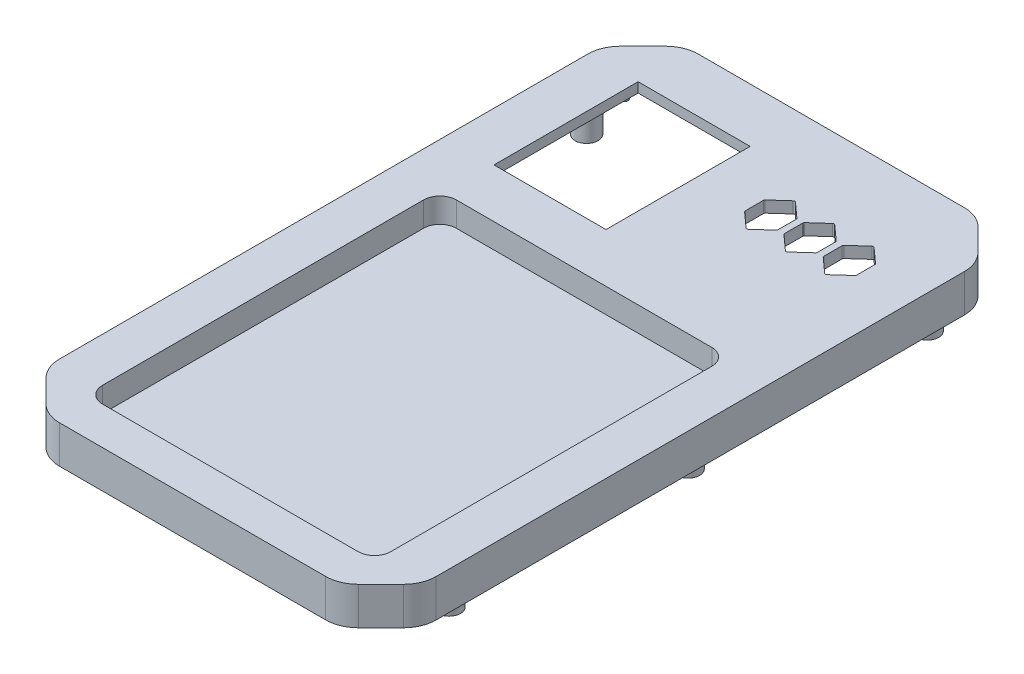
SolidWorks part; units mm, degrees
ref_plane "Front Plane" through (0, 0, 0) normal (0, 0, 1) x (1, 0, 0)
ref_plane "Top Plane" through (0, 0, 0) normal (0, 1, 0) x (1, 0, 0)
ref_plane "Right Plane" through (0, 0, 0) normal (1, 0, 0) x (0, 0, -1)
sketch "Sketch1" plane through (0, 0, 0) normal (0, 1, 0) x (1, 0, 0)
  line L0 (12.7279, 12.7279) -> (102.2721, 12.7279)
  line L1 (115, 0) -> (115, -169.5442)
  line L2 (102.2721, -182.2721) -> (12.7279, -182.2721)
  line L3 (0, -169.5442) -> (0, 0)
  line L4 (12.7279, 12.7279) -> (0, 0)
  line L5 (102.2721, 12.7279) -> (115, 0)
  line L6 (0, -169.5442) -> (12.7279, -182.2721)
  line L7 (115, -169.5442) -> (102.2721, -182.2721)
  dimension "D1" = 115
  dimension "D2" = 195
  dimension "D3" = 135
  dimension "D4" = 135
  dimension "D5" = 135
  dimension "D6" = 135
  dimension "D7" = 18
extrude "Boss-Extrude4" add sketch "Sketch1" along normal blind 20
fillet "Fillet4" radius 10 8 edges at (115, 10, 0) (115, 10, 169.5442) (12.7279, 10, 182.2721) (0, 10, 169.5442) (0, 10, 0) (12.7279, 10, -12.7279) (102.2721, 10, -12.7279) (102.2721, 10, 182.2721)
sketch "Sketch5" plane through (0, 20, 0) normal (0, 1, 0) x (1, 0, 0)
  line L0 (0, -4.1421) -> (0, -165.402) construction
  line L2 (16.8701, -182.2721) -> (98.1299, -182.2721) construction
  line L4 (15, -3.7721) -> (49.2, -3.7721)
  line L5 (15, -3.7721) -> (15, -47.7721)
  line L6 (15, -47.7721) -> (49.2, -47.7721)
  line L7 (49.2, -3.7721) -> (49.2, -47.7721)
  line L8 (96.5, -62.7721) -> (18.5, -62.7721)
  line L9 (101.5, -165.7721) -> (101.5, -67.7721)
  line L10 (18.5, -170.7721) -> (96.5, -170.7721)
  line L11 (13.5, -67.7721) -> (13.5, -165.7721)
  arc A1 (18.5, -62.7721) -> (13.5, -67.7721) centre (18.5, -67.7721) ccw
  arc A2 (96.5, -170.7721) -> (101.5, -165.7721) centre (96.5, -165.7721) ccw
  arc A3 (101.5, -67.7721) -> (96.5, -62.7721) centre (96.5, -67.7721) ccw
  arc A4 (13.5, -165.7721) -> (18.5, -170.7721) centre (18.5, -165.7721) ccw
  dimension "D3" = 13.5
  dimension "D9" = 10
  dimension "D1" = 34.2
  dimension "D5" = 88
  dimension "D2" = 44
  dimension "D4" = 11.5
  dimension "D6" = 108
  dimension "D7" = 15
  dimension "D8" = 15
extrude "Cut-Extrude4" cut sketch "Sketch5" against normal blind 7.5
ref_plane "Plane1" through (0, 6.25, 0) normal (0, 1, 0) x (1, 0, 0)
sketch "Sketch23" plane through (0, 20, 0) normal (0, 1, 0) x (1, 0, 0)
  line L0 (99.5, -21.7721) -> (99.5, -15.7721)
  line L23 (99.5, -15.7721) -> (94.5, -11.2721)
  line L24 (94.5, -11.2721) -> (89.5, -15.7721)
  line L29 (89.5, -15.7721) -> (89.5, -21.7721)
  line L30 (89.5, -21.7721) -> (94.5, -26.2721)
  line L35 (94.5, -26.2721) -> (99.5, -21.7721)
  line L36 (87.5, -21.7721) -> (87.5, -15.7721)
  line L37 (75.5, -21.7721) -> (75.5, -15.7721)
  line L38 (75.5, -15.7721) -> (70.5, -11.2721)
  line L39 (70.5, -11.2721) -> (65.5, -15.7721)
  line L40 (65.5, -15.7721) -> (65.5, -21.7721)
  line L41 (65.5, -21.7721) -> (70.5, -26.2721)
  line L42 (70.5, -26.2721) -> (75.5, -21.7721)
  line L43 (87.5, -15.7721) -> (82.5, -11.2721)
  line L44 (82.5, -11.2721) -> (77.5, -15.7721)
  line L45 (77.5, -15.7721) -> (77.5, -21.7721)
  line L46 (77.5, -21.7721) -> (82.5, -26.2721)
  line L47 (82.5, -26.2721) -> (87.5, -21.7721)
  line L50 (94.5, -11.2721) -> (94.5, -26.2721) construction
  line L51 (89.5, -18.7721) -> (99.5, -18.7721) construction
  line L52 (98.1299, 12.7279) -> (16.8701, 12.7279) construction
  line L53 (82.5, -11.2721) -> (82.5, -26.2721) construction
  line L54 (70.5, -11.2721) -> (70.5, -26.2721) construction
  line L55 (115, -165.402) -> (115, -4.1421) construction
  point P16 (94.5, -18.7721)
  dimension "D1" = 10
  dimension "D2" = 15
  dimension "D3" = 10
  dimension "D4" = 15
  dimension "D5" = 10
  dimension "D6" = 15
  dimension "D7" = 20.5
  dimension "D8" = 12
  dimension "D9" = 6
  dimension "D10" = 12
  dimension "D11" = 31.5
sketch "Sketch28" plane through (0, 0, 0) normal (0, -1, 0) x (1, 0, 0)
  line L0 (98.1299, -12.7279) -> (16.8701, -12.7279) construction
  line L1 (105, 57.2721) -> (56, 57.2721)
  line L2 (105, 57.2721) -> (105, 22.2721)
  line L3 (105, 22.2721) -> (56, 22.2721)
  line L4 (56, 57.2721) -> (56, 22.2721)
  line L5 (115, 165.402) -> (115, 4.1421) construction
  dimension "D5" = 10
  dimension "D6" = 49
  dimension "D7" = 35
  dimension "D1" = 35
extrude "Cut-Extrude17" cut sketch "Sketch28" against normal blind 13
shell "Shell2" thickness 1.5
extrude "Cut-Extrude15" cut sketch "Sketch23" against normal up to next
fillet "Fillet3" radius 0.5 18 edges at (82.5, 19.25, 26.2721) (94.5, 19.25, 26.2721) (89.5, 19.25, 21.7721) (89.5, 19.25, 15.7721) (77.5, 19.25, 21.7721) (77.5, 19.25, 15.7721) (70.5, 19.25, 26.2721) (65.5, 19.25, 21.7721) (75.5, 19.25, 21.7721) (75.5, 19.25, 15.7721) (87.5, 19.25, 15.7721) (99.5, 19.25, 21.7721) (99.5, 19.25, 15.7721) (94.5, 19.25, 11.2721) (82.5, 19.25, 11.2721) (65.5, 19.25, 15.7721) (70.5, 19.25, 11.2721) (87.5, 19.25, 21.7721)
sketch "Sketch29" plane through (0, 12.5, 0) normal (0, 1, 0) x (1, 0, 0)
  line L4 (49.2, -3.7721) -> (15, -3.7721)
  line L5 (15, -3.7721) -> (15, -47.7721)
  line L6 (15, -47.7721) -> (49.2, -47.7721)
  line L7 (49.2, -47.7721) -> (49.2, -3.7721)
  line L8 (49.2, -3.7721) -> (15, -3.7721)
  line L9 (15, -3.7721) -> (15, -47.7721)
  line L10 (15, -47.7721) -> (49.2, -47.7721)
  line L11 (49.2, -47.7721) -> (49.2, -3.7721)
  dimension "D1" = 0
extrude "Cut-Extrude18" cut sketch "Sketch29" against normal up to next
sketch "Sketch30" plane through (0, 13, 0) normal (0, -1, 0) x (1, 0, 0)
  line L0 (58, 45.1221) -> (103, 45.1221)
  line L3 (58, 46.5721) -> (103, 46.5721)
  line L6 (58, 34.4221) -> (103, 34.4221)
  line L8 (56, 57.2721) -> (56, 22.2721) construction
  line L9 (105, 22.2721) -> (105, 57.2721) construction
  line L10 (58, 32.9721) -> (103, 32.9721)
  line L14 (105, 22.2721) -> (105, 57.2721) construction
  line L15 (105, 57.2721) -> (56, 57.2721) construction
  line L20 (103, 49.3221) -> (104, 49.3221)
  line L21 (56, 22.2721) -> (105, 22.2721) construction
  line L22 (57, 49.3221) -> (58, 49.3221)
  line L23 (57, 49.3221) -> (57, 42.8221)
  line L24 (57, 42.8221) -> (58, 42.8221)
  line L25 (58, 49.3221) -> (58, 46.5721)
  line L26 (103, 49.3221) -> (103, 46.5721)
  line L27 (103, 42.8221) -> (104, 42.8221)
  line L28 (57, 37.1721) -> (58, 37.1721)
  line L29 (57, 37.1721) -> (57, 30.6721)
  line L30 (57, 30.6721) -> (58, 30.6721)
  line L31 (58, 37.1721) -> (58, 34.4221)
  line L32 (104, 49.3221) -> (104, 42.8221)
  line L33 (103, 37.1721) -> (104, 37.1721)
  line L34 (103, 37.1721) -> (103, 34.4221)
  line L35 (103, 30.6721) -> (104, 30.6721)
  line L36 (104, 37.1721) -> (104, 30.6721)
  line L37 (58, 45.1221) -> (58, 42.8221)
  line L38 (103, 45.1221) -> (103, 42.8221)
  line L39 (103, 32.9721) -> (103, 30.6721)
  line L40 (58, 32.9721) -> (58, 30.6721)
  point P14 (57.5, 42.8221)
  point P33 (57.5, 30.6721)
  dimension "D1" = 10.7
  dimension "D2" = 10.7
  dimension "D3" = 1.45
  dimension "D4" = 10.7
  dimension "D5" = 1
  dimension "D6" = 6.5
  dimension "D7" = 2.75
  dimension "D8" = 1
  dimension "D9" = 2.75
  dimension "D10" = 1
  dimension "D11" = 6.5
  dimension "D12" = 1
  dimension "D13" = 1
  dimension "D14" = 1
extrude "Boss-Extrude11" add sketch "Sketch30" along normal blind 9 contours L40 L10 L39 L35 L36 L33 L34 L6 L31 L28 L29 L30 | L0 L38 L27 L32 L20 L26 L3 L25 L22 L23 L24 L37 | L0 L38 L27 L32 L20 L26 L3 L25 L22 L23 L24 L37 | L28 L31 L6 L34 L33 L36 L35 L39 L10 L40 L30 L29 region at (80.5, 13, 45.8845) region at (80.5, 13, 33.7345)
sketch "Sketch33" plane through (0, 14.5, 0) normal (0, 1, 0) x (1, 0, 0)
  line L6 (54.5, -50.1721) -> (56, -50.1721)
  line L7 (54.5, -50.1721) -> (54.5, -54.7721)
  line L8 (54.5, -54.7721) -> (56, -54.7721)
  line L9 (56, -50.1721) -> (56, -54.7721)
  line L10 (106.5, -58.7721) -> (54.5, -58.7721) construction
  line L11 (105, -24.7721) -> (106.5, -24.7721)
  line L12 (105, -24.7721) -> (105, -29.3721)
  line L13 (105, -29.3721) -> (106.5, -29.3721)
  line L14 (106.5, -24.7721) -> (106.5, -29.3721)
  line L15 (106.5, -20.7721) -> (106.5, -58.7721) construction
  line L16 (54.5, -20.7721) -> (106.5, -20.7721) construction
  line L18 (54.5, -58.7721) -> (54.5, -20.7721) construction
  line L22 (56, -57.2721) -> (105, -57.2721)
  line L23 (56, -22.2721) -> (56, -57.2721)
  line L24 (105, -22.2721) -> (56, -22.2721)
  line L25 (105, -57.2721) -> (105, -22.2721)
  line L26 (56, -57.2721) -> (105, -57.2721)
  line L27 (56, -22.2721) -> (56, -57.2721)
  line L28 (105, -22.2721) -> (56, -22.2721)
  line L29 (105, -57.2721) -> (105, -22.2721)
  dimension "D1" = 4
  dimension "D2" = 4.6
  dimension "D4" = 4.6
  dimension "D6" = 4
  dimension "D7" = 0
extrude "Cut-Extrude19" cut sketch "Sketch33" against normal blind 3 contours L7 L8 L9 L6 | L14 L13 L12 L11
sketch "Sketch34" plane through (0, 0, 0) normal (0, -1, 0) x (1, 0, 0)
  line L0 (105, 57.2721) -> (56, 57.2721) construction
  line L1 (106, 58.2721) -> (55, 58.2721)
  line L2 (106, 58.2721) -> (106, 21.2721)
  line L3 (106, 21.2721) -> (55, 21.2721)
  line L4 (55, 58.2721) -> (55, 21.2721)
  line L5 (56, 22.2721) -> (105, 22.2721) construction
  line L6 (56, 57.2721) -> (56, 22.2721) construction
  line L7 (104, 37.1721) -> (104, 30.6721) construction
  dimension "D1" = 1
  dimension "D2" = 1
  dimension "D3" = 1
  dimension "D4" = 2
extrude "Cut-Extrude22" cut sketch "Sketch34" against normal blind 3
sketch "Sketch37" plane through (0, 1.5, 0) normal (0, 1, 0) x (1, 0, 0)
  line L0 (54.5, -20.7721) -> (106.5, -20.7721) construction
  line L1 (68, -9.7721) -> (93, -9.7721)
  line L2 (68, -9.7721) -> (68, -20.7721)
  line L3 (68, -20.7721) -> (93, -20.7721)
  line L4 (93, -9.7721) -> (93, -20.7721)
  line L6 (54.5, -20.7721) -> (106.5, -20.7721) construction
  point P8 (80.5, -20.7721)
  dimension "D1" = 11
  dimension "D2" = 25
extrude "Boss-Extrude13" add sketch "Sketch37" along normal blind 7
sketch "Sketch35" plane through (0, 0, 0) normal (0, -1, 0) x (1, 0, 0)
  line L0 (55, 21.2721) -> (106, 21.2721) construction
  line L1 (55, 21.2721) -> (106, 21.2721) construction
  line L2 (88.5, 21.2721) -> (72.5, 21.2721)
  arc A0 (88.5, 21.2721) -> (72.5, 21.2721) centre (80.5, 21.2721) cw
  point P7 (80.5, 13.2721)
  dimension "D1" = 8
extrude "Cut-Extrude25" cut sketch "Sketch35" against normal blind 3
sketch "Sketch38" plane through (0, 3, 0) normal (0, -1, 0) x (1, 0, 0)
  line L0 (56, 22.2721) -> (105, 22.2721) construction
  circle A0 centre (80.5, 18.2721) radius 1.5
  dimension "D1" = 3
  dimension "D2" = 4
  dimension "D3" = 8
extrude "Cut-Extrude26" cut sketch "Sketch38" against normal blind 5
sketch "Sketch39" plane through (0, 0, 58.2721) normal (0, 0, -1) x (-1, 0, 0)
  line L0 (-106, 3) -> (-55, 3) construction
  line L1 (-98, 3) -> (-91, 3)
  line L2 (-98, 3) -> (-98, 1)
  line L3 (-98, 1) -> (-91, 1)
  line L4 (-91, 3) -> (-91, 1)
  line L5 (-105, 3) -> (-56, 3) construction
  line L6 (-103, 4) -> (-103, 13) construction
  line L7 (-70, 3) -> (-63, 3)
  line L8 (-70, 3) -> (-70, 1)
  line L9 (-70, 1) -> (-63, 1)
  line L10 (-63, 3) -> (-63, 1)
  line L12 (-58, 4) -> (-58, 13) construction
  dimension "D1" = 7
  dimension "D2" = 2
  dimension "D3" = 5
  dimension "D4" = 7
  dimension "D5" = 2
  dimension "D6" = 5
extrude "Cut-Extrude27" cut sketch "Sketch39" against normal blind 5
ref_plane "Plane5" through (0, 8.8, 0) normal (0, -1, 0) x (-1, 0, 0)
sketch "Sketch40" plane through (0, 0, 0) normal (0, -1, 0) x (1, 0, 0)
  line L8 (105.201, -9.799) -> (112.0711, -2.9289)
  line L9 (115, 4.1421) -> (115, 165.402)
  line L10 (112.0711, 172.4731) -> (105.201, 179.3431)
  line L11 (98.1299, 182.2721) -> (16.8701, 182.2721)
  line L12 (9.799, 179.3431) -> (2.9289, 172.4731)
  line L13 (0, 165.402) -> (0, 4.1421)
  line L14 (2.9289, -2.9289) -> (9.799, -9.799)
  line L15 (16.8701, -12.7279) -> (98.1299, -12.7279)
  line L16 (105.201, -9.799) -> (112.0711, -2.9289)
  line L17 (115, 4.1421) -> (115, 165.402)
  line L18 (112.0711, 172.4731) -> (105.201, 179.3431)
  line L19 (98.1299, 182.2721) -> (16.8701, 182.2721)
  line L20 (9.799, 179.3431) -> (2.9289, 172.4731)
  line L21 (0, 165.402) -> (0, 4.1421)
  line L22 (2.9289, -2.9289) -> (9.799, -9.799)
  line L23 (16.8701, -12.7279) -> (98.1299, -12.7279)
  line L24 (98.1299, 177.2721) -> (16.8701, 177.2721)
  line L25 (13.3345, 175.8076) -> (6.4645, 168.9376)
  line L26 (5, 165.402) -> (5, 4.1421)
  line L27 (6.4645, 0.6066) -> (13.3345, -6.2635)
  line L28 (16.8701, -7.7279) -> (98.1299, -7.7279)
  line L29 (101.6655, -6.2635) -> (108.5355, 0.6066)
  line L30 (110, 4.1421) -> (110, 165.402)
  line L31 (108.5355, 168.9376) -> (101.6655, 175.8076)
  arc A0 (16.8701, 177.2721) -> (13.3345, 175.8076) centre (16.8701, 172.2721) ccw
  arc A1 (6.4645, 168.9376) -> (5, 165.402) centre (10, 165.402) ccw
  arc A2 (5, 4.1421) -> (6.4645, 0.6066) centre (10, 4.1421) ccw
  arc A3 (13.3345, -6.2635) -> (16.8701, -7.7279) centre (16.8701, -2.7279) ccw
  arc A4 (98.1299, -7.7279) -> (101.6655, -6.2635) centre (98.1299, -2.7279) ccw
  arc A5 (108.5355, 0.6066) -> (110, 4.1421) centre (105, 4.1421) ccw
  arc A6 (110, 165.402) -> (108.5355, 168.9376) centre (105, 165.402) ccw
  arc A7 (101.6655, 175.8076) -> (98.1299, 177.2721) centre (98.1299, 172.2721) ccw
  arc A8 (112.0711, -2.9289) -> (115, 4.1421) centre (105, 4.1421) ccw
  arc A9 (112.0711, -2.9289) -> (115, 4.1421) centre (105, 4.1421) ccw
  arc A10 (115, 165.402) -> (112.0711, 172.4731) centre (105, 165.402) ccw
  arc A11 (115, 165.402) -> (112.0711, 172.4731) centre (105, 165.402) ccw
  arc A12 (105.201, 179.3431) -> (98.1299, 182.2721) centre (98.1299, 172.2721) ccw
  arc A13 (105.201, 179.3431) -> (98.1299, 182.2721) centre (98.1299, 172.2721) ccw
  arc A14 (16.8701, 182.2721) -> (9.799, 179.3431) centre (16.8701, 172.2721) ccw
  arc A15 (16.8701, 182.2721) -> (9.799, 179.3431) centre (16.8701, 172.2721) ccw
  arc A16 (2.9289, 172.4731) -> (0, 165.402) centre (10, 165.402) ccw
  arc A17 (2.9289, 172.4731) -> (0, 165.402) centre (10, 165.402) ccw
  arc A18 (0, 4.1421) -> (2.9289, -2.9289) centre (10, 4.1421) ccw
  arc A19 (0, 4.1421) -> (2.9289, -2.9289) centre (10, 4.1421) ccw
  arc A20 (9.799, -9.799) -> (16.8701, -12.7279) centre (16.8701, -2.7279) ccw
  arc A21 (9.799, -9.799) -> (16.8701, -12.7279) centre (16.8701, -2.7279) ccw
  arc A22 (98.1299, -12.7279) -> (105.201, -9.799) centre (98.1299, -2.7279) ccw
  arc A23 (98.1299, -12.7279) -> (105.201, -9.799) centre (98.1299, -2.7279) ccw
  dimension "D1" = 0
  dimension "D2" = 5
extrude "Cut-Extrude28" cut sketch "Sketch40" against normal blind 10
delete or keep bodies "Body-Delete/Keep 1" type delete bodies bodies 175
sketch "Sketch42" plane through (0, 10, 0) normal (0, -1, 0) x (1, 0, 0)
  line L8 (16.8701, -12.7279) -> (98.1299, -12.7279)
  line L9 (105.201, -9.799) -> (112.0711, -2.9289)
  line L10 (115, 4.1421) -> (115, 165.402)
  line L11 (112.0711, 172.4731) -> (105.201, 179.3431)
  line L12 (98.1299, 182.2721) -> (16.8701, 182.2721)
  line L13 (9.799, 179.3431) -> (2.9289, 172.4731)
  line L14 (0, 165.402) -> (0, 4.1421)
  line L15 (2.9289, -2.9289) -> (9.799, -9.799)
  line L16 (16.8701, -12.7279) -> (98.1299, -12.7279)
  line L17 (105.201, -9.799) -> (112.0711, -2.9289)
  line L18 (115, 4.1421) -> (115, 165.402)
  line L19 (112.0711, 172.4731) -> (105.201, 179.3431)
  line L20 (98.1299, 182.2721) -> (16.8701, 182.2721)
  line L21 (9.799, 179.3431) -> (2.9289, 172.4731)
  line L22 (0, 165.402) -> (0, 4.1421)
  line L23 (2.9289, -2.9289) -> (9.799, -9.799)
  line L24 (10.2233, 178.9189) -> (3.3532, 172.0488)
  line L25 (0.6, 165.402) -> (0.6, 4.1421)
  line L26 (3.3532, -2.5047) -> (10.2233, -9.3747)
  line L27 (16.8701, -12.1279) -> (98.1299, -12.1279)
  line L28 (104.7767, -9.3747) -> (111.6468, -2.5047)
  line L29 (114.4, 4.1421) -> (114.4, 165.402)
  line L30 (111.6468, 172.0488) -> (104.7767, 178.9189)
  line L31 (98.1299, 181.6721) -> (16.8701, 181.6721)
  arc A0 (16.8701, 181.6721) -> (10.2233, 178.9189) centre (16.8701, 172.2721) ccw
  arc A1 (3.3532, 172.0488) -> (0.6, 165.402) centre (10, 165.402) ccw
  arc A2 (0.6, 4.1421) -> (3.3532, -2.5047) centre (10, 4.1421) ccw
  arc A3 (10.2233, -9.3747) -> (16.8701, -12.1279) centre (16.8701, -2.7279) ccw
  arc A4 (98.1299, -12.1279) -> (104.7767, -9.3747) centre (98.1299, -2.7279) ccw
  arc A5 (111.6468, -2.5047) -> (114.4, 4.1421) centre (105, 4.1421) ccw
  arc A6 (114.4, 165.402) -> (111.6468, 172.0488) centre (105, 165.402) ccw
  arc A7 (104.7767, 178.9189) -> (98.1299, 181.6721) centre (98.1299, 172.2721) ccw
  arc A8 (112.0711, -2.9289) -> (115, 4.1421) centre (105, 4.1421) ccw
  arc A9 (112.0711, -2.9289) -> (115, 4.1421) centre (105, 4.1421) ccw
  arc A10 (115, 165.402) -> (112.0711, 172.4731) centre (105, 165.402) ccw
  arc A11 (115, 165.402) -> (112.0711, 172.4731) centre (105, 165.402) ccw
  arc A12 (105.201, 179.3431) -> (98.1299, 182.2721) centre (98.1299, 172.2721) ccw
  arc A13 (105.201, 179.3431) -> (98.1299, 182.2721) centre (98.1299, 172.2721) ccw
  arc A14 (16.8701, 182.2721) -> (9.799, 179.3431) centre (16.8701, 172.2721) ccw
  arc A15 (16.8701, 182.2721) -> (9.799, 179.3431) centre (16.8701, 172.2721) ccw
  arc A16 (2.9289, 172.4731) -> (0, 165.402) centre (10, 165.402) ccw
  arc A17 (2.9289, 172.4731) -> (0, 165.402) centre (10, 165.402) ccw
  arc A18 (0, 4.1421) -> (2.9289, -2.9289) centre (10, 4.1421) ccw
  arc A19 (0, 4.1421) -> (2.9289, -2.9289) centre (10, 4.1421) ccw
  arc A20 (9.799, -9.799) -> (16.8701, -12.7279) centre (16.8701, -2.7279) ccw
  arc A21 (9.799, -9.799) -> (16.8701, -12.7279) centre (16.8701, -2.7279) ccw
  arc A22 (98.1299, -12.7279) -> (105.201, -9.799) centre (98.1299, -2.7279) ccw
  arc A23 (98.1299, -12.7279) -> (105.201, -9.799) centre (98.1299, -2.7279) ccw
  dimension "D1" = 0
  dimension "D2" = 0.6
extrude "Boss-Extrude14" add sketch "Sketch42" along normal blind 1.5
sketch "Sketch45" plane through (0, 0, 0) normal (0, 1, 0) x (1, 0, 0)
  line L0 (5.5, -10) -> (5.5, -83) construction
  line L1 (5.5, -83) -> (5.5, -156) construction
  line L2 (5.5, -156) -> (109.5, -156) construction
  line L3 (109.5, -156) -> (109.5, -83) construction
  line L4 (109.5, -83) -> (109.5, -10) construction
  line L5 (109.5, -10) -> (5.5, -10) construction
  line L6 (5.5, -83) -> (109.5, -83) construction
  line L7 (57.5, 12.7279) -> (57.5, -30.3618) construction
  line L8 (98.1299, 12.7279) -> (16.8701, 12.7279) construction
  circle A0 centre (5.5, -10) radius 4
  circle A1 centre (109.5, -10) radius 4
  circle A2 centre (109.5, -156) radius 4
  circle A3 centre (5.5, -156) radius 4
  circle A4 centre (5.5, -83) radius 4
  circle A5 centre (109.5, -83) radius 4
  dimension "D5" = 8
  dimension "D1" = 10
  dimension "D2" = 73
  dimension "D3" = 104
sketch "Sketch46" plane through (0, 18.5, 0) normal (0, -1, 0) x (1, 0, 0)
  circle A0 centre (5.5, 83) radius 3.5
  circle A1 centre (5.5, 10) radius 3.5
  circle A2 centre (109.5, 10) radius 3.5
  circle A3 centre (109.5, 83) radius 3.5
  circle A4 centre (109.5, 156) radius 3.5
  circle A5 centre (5.5, 156) radius 3.5
  dimension "D2" = 7
extrude "Boss-Extrude16" add sketch "Sketch46" along normal blind 14
sketch "Sketch51" plane through (0, 4.5, 0) normal (0, -1, 0) x (1, 0, 0)
  circle A0 centre (5.5, 156) radius 0.6
  dimension "D1" = 1.2
sketch "Sketch52" plane through (0, 4.5, 0) normal (0, -1, 0) x (1, 0, 0)
  circle A1 centre (5.5, 10) radius 0.6
  circle A2 centre (109.5, 10) radius 0.6
  circle A6 centre (5.5, 156) radius 0.6 construction
  circle A7 centre (5.5, 156) radius 0.6
  circle A8 centre (109.5, 156) radius 0.6
  circle A9 centre (109.5, 83) radius 0.6
  circle A10 centre (5.5, 83) radius 0.6
extrude "Cut-Extrude30" cut sketch "Sketch52" against normal blind 12
ref_plane "Plane6" through (70, 0, 0) normal (1, 0, 0) x (0, 0, -1)
sketch "Sketch53" plane through (70, 0, 0) normal (1, 0, 0) x (0, 0, -1)
  line L0 (-61.2721, 11) -> (-61.2721, 12.079)
  line L1 (-61.2721, 11) -> (-61.2721, 18.5) construction
  line L2 (-61.2721, 12.079) -> (-62.5603, 11)
  line L3 (-67.7721, 11) -> (-61.2721, 11) construction
  line L4 (-62.5603, 11) -> (-61.2721, 11)
  dimension "D1" = 1.079
  dimension "D2" = 1.6804
extrude "Cut-Extrude31" cut sketch "Sketch53" against normal up to next and the other way up to next
sketch "Sketch54" plane through (0, 11, 0) normal (0, -1, 0) x (1, 0, 0)
  line L4 (50.7, 2.2721) -> (50.7, 49.2721)
  line L5 (50.7, 49.2721) -> (13.5, 49.2721)
  line L6 (13.5, 49.2721) -> (13.5, 2.2721)
  line L7 (13.5, 2.2721) -> (50.7, 2.2721)
  line L8 (50.7, 2.2721) -> (50.7, 49.2721)
  line L9 (50.7, 49.2721) -> (13.5, 49.2721)
  line L10 (13.5, 49.2721) -> (13.5, 2.2721)
  line L11 (13.5, 2.2721) -> (50.7, 2.2721)
  dimension "D1" = 0
extrude "Cut-Extrude33" cut sketch "Sketch54" against normal blind 6
sketch "Sketch57" plane through (0, 17, 0) normal (0, -1, 0) x (1, 0, 0)
  line L0 (32.1, 47.7721) -> (32.1, 3.7721) construction
  line L1 (9.6, -1.2279) -> (54.6, -1.2279)
  line L2 (9.6, -1.2279) -> (9.6, 52.7721)
  line L3 (9.6, 52.7721) -> (54.6, 52.7721)
  line L4 (54.6, -1.2279) -> (54.6, 52.7721)
  line L5 (9.6, -1.2279) -> (54.6, 52.7721) construction
  line L6 (9.6, 52.7721) -> (54.6, -1.2279) construction
  line L7 (15, 47.7721) -> (49.2, 47.7721) construction
  line L8 (49.2, 3.7721) -> (15, 3.7721) construction
  line L9 (15, 25.7721) -> (49.2, 25.7721) construction
  line L10 (15, 3.7721) -> (15, 47.7721) construction
  line L11 (49.2, 47.7721) -> (49.2, 3.7721) construction
  line L12 (50.7, 49.2721) -> (50.7, 2.2721) construction
  line L13 (50.7, 2.2721) -> (13.5, 2.2721) construction
  line L14 (13.5, 49.2721) -> (13.5, 2.2721) construction
  line L15 (50.7, 49.2721) -> (13.5, 49.2721) construction
  line L16 (50.7, 49.2721) -> (50.7, 2.2721)
  line L17 (50.7, 2.2721) -> (13.5, 2.2721)
  line L18 (13.5, 49.2721) -> (13.5, 2.2721)
  line L19 (50.7, 49.2721) -> (13.5, 49.2721)
  point P0 (32.1, 25.7721)
  dimension "D1" = 45
  dimension "D2" = 54
extrude "Boss-Extrude17" add sketch "Sketch57" against normal up to next
sketch "Sketch58" plane through (0, 17, 0) normal (0, -1, 0) x (1, 0, 0)
  line L0 (9.6, 52.7721) -> (9.6, -1.2279) construction
  line L1 (9.6, 52.7721) -> (54.6, 52.7721) construction
  circle A0 centre (12.3, 5.3321) radius 1.2
  circle A1 centre (52.4, 5.3321) radius 1.2
  circle A2 centre (52.4, 50.3321) radius 1.2
  circle A3 centre (12.3, 50.3321) radius 1.2
  dimension "D1" = 2.4
  dimension "D2" = 2.7
  dimension "D3" = 2.44
  dimension "D4" = 45
  dimension "D5" = 40.1
extrude "Boss-Extrude18" add sketch "Sketch58" along normal blind 2
sketch "Sketch59" plane through (0, 11, 0) normal (0, -1, 0) x (1, 0, 0)
  line L0 (12, 59.2721) -> (103, 59.2721)
  line L1 (96.5, 61.2721) -> (18.5, 61.2721) construction
  line L4 (14.6158, 62.5603) -> (100.3842, 62.5603)
  line L5 (103, 67.7721) -> (103, 165.7721)
  line L6 (96.5, 172.2721) -> (18.5, 172.2721)
  line L7 (12, 165.7721) -> (12, 67.7721)
  line L9 (103, 59.2721) -> (103, 165.7721)
  line L10 (96.5, 172.2721) -> (18.5, 172.2721)
  line L11 (12, 165.7721) -> (12, 59.2721)
  arc A4 (100.3842, 62.5603) -> (103, 67.7721) centre (96.5, 67.7721) ccw
  arc A5 (103, 165.7721) -> (96.5, 172.2721) centre (96.5, 165.7721) ccw
  arc A6 (18.5, 172.2721) -> (12, 165.7721) centre (18.5, 165.7721) ccw
  arc A7 (12, 67.7721) -> (14.6158, 62.5603) centre (18.5, 67.7721) ccw
  arc A9 (103, 165.7721) -> (96.5, 172.2721) centre (96.5, 165.7721) ccw
  arc A10 (18.5, 172.2721) -> (12, 165.7721) centre (18.5, 165.7721) ccw
  dimension "D2" = 2
  dimension "D1" = 0
extrude "Cut-Extrude34" cut sketch "Sketch59" against normal blind 0.5
sketch "Sketch60" plane through (0, 18.5, 0) normal (0, -1, 0) x (1, 0, 0)
  line L6 (94.1655, 25.971) -> (89.6655, 21.921)
  line L7 (99.3345, 21.921) -> (94.8345, 25.971)
  line L8 (99.5, 15.9948) -> (99.5, 21.5494)
  line L9 (94.8345, 11.5731) -> (99.3345, 15.6231)
  line L10 (89.6655, 15.6231) -> (94.1655, 11.5731)
  line L11 (89.5, 21.5494) -> (89.5, 15.9948)
  line L12 (94.1655, 25.971) -> (89.6655, 21.921)
  line L13 (99.3345, 21.921) -> (94.8345, 25.971)
  line L14 (99.5, 15.9948) -> (99.5, 21.5494)
  line L15 (94.8345, 11.5731) -> (99.3345, 15.6231)
  line L16 (89.6655, 15.6231) -> (94.1655, 11.5731)
  line L17 (89.5, 21.5494) -> (89.5, 15.9948)
  line L18 (82.1655, 25.971) -> (77.6655, 21.921)
  line L19 (87.3345, 21.921) -> (82.8345, 25.971)
  line L20 (87.5, 15.9948) -> (87.5, 21.5494)
  line L21 (82.8345, 11.5731) -> (87.3345, 15.6231)
  line L22 (77.6655, 15.6231) -> (82.1655, 11.5731)
  line L23 (77.5, 21.5494) -> (77.5, 15.9948)
  line L24 (82.1655, 25.971) -> (77.6655, 21.921)
  line L25 (87.3345, 21.921) -> (82.8345, 25.971)
  line L26 (87.5, 15.9948) -> (87.5, 21.5494)
  line L27 (82.8345, 11.5731) -> (87.3345, 15.6231)
  line L28 (77.6655, 15.6231) -> (82.1655, 11.5731)
  line L29 (77.5, 21.5494) -> (77.5, 15.9948)
  line L30 (70.1655, 25.971) -> (65.6655, 21.921)
  line L31 (75.3345, 21.921) -> (70.8345, 25.971)
  line L32 (75.5, 15.9948) -> (75.5, 21.5494)
  line L33 (70.8345, 11.5731) -> (75.3345, 15.6231)
  line L34 (65.6655, 15.6231) -> (70.1655, 11.5731)
  line L35 (65.5, 21.5494) -> (65.5, 15.9948)
  line L36 (70.1655, 25.971) -> (65.6655, 21.921)
  line L37 (75.3345, 21.921) -> (70.8345, 25.971)
  line L38 (75.5, 15.9948) -> (75.5, 21.5494)
  line L39 (70.8345, 11.5731) -> (75.3345, 15.6231)
  line L40 (65.6655, 15.6231) -> (70.1655, 11.5731)
  line L41 (65.5, 21.5494) -> (65.5, 15.9948)
  line L48 (69.3628, 26.863) -> (64.8628, 22.813)
  line L49 (64.3, 21.5494) -> (64.3, 15.9948)
  line L50 (64.8628, 14.7312) -> (69.3628, 10.6812)
  line L51 (71.6372, 10.6812) -> (76.1372, 14.7312)
  line L53 (76.1372, 22.813) -> (71.6372, 26.863)
  line L54 (81.3628, 26.863) -> (76.8628, 22.813)
  line L56 (76.8628, 14.7312) -> (81.3628, 10.6812)
  line L57 (83.6372, 10.6812) -> (88.1372, 14.7312)
  line L59 (88.1372, 22.813) -> (83.6372, 26.863)
  line L60 (93.3628, 26.863) -> (88.8628, 22.813)
  line L62 (88.8628, 14.7312) -> (93.3628, 10.6812)
  line L63 (95.6372, 10.6812) -> (100.1372, 14.7312)
  line L64 (100.7, 15.9948) -> (100.7, 21.5494)
  line L76 (100.1372, 22.813) -> (95.6372, 26.863)
  line L88 (76.7, 15.9948) -> (76.7, 21.5494) construction
  line L89 (76.3, 21.5494) -> (76.3, 15.9948) construction
  line L90 (88.7, 15.9948) -> (88.7, 21.5494) construction
  line L91 (88.3, 21.5494) -> (88.3, 15.9948) construction
  arc A5 (82.8345, 25.971) -> (82.1655, 25.971) centre (82.5, 25.5994) ccw
  arc A6 (94.8345, 25.971) -> (94.1655, 25.971) centre (94.5, 25.5994) ccw
  arc A7 (99.5, 21.5494) -> (99.3345, 21.921) centre (99, 21.5494) ccw
  arc A8 (99.3345, 15.6231) -> (99.5, 15.9948) centre (99, 15.9948) ccw
  arc A9 (94.1655, 11.5731) -> (94.8345, 11.5731) centre (94.5, 11.9448) ccw
  arc A10 (89.5, 15.9948) -> (89.6655, 15.6231) centre (90, 15.9948) ccw
  arc A11 (89.6655, 21.921) -> (89.5, 21.5494) centre (90, 21.5494) ccw
  arc A12 (94.8345, 25.971) -> (94.1655, 25.971) centre (94.5, 25.5994) ccw
  arc A13 (99.5, 21.5494) -> (99.3345, 21.921) centre (99, 21.5494) ccw
  arc A14 (99.3345, 15.6231) -> (99.5, 15.9948) centre (99, 15.9948) ccw
  arc A15 (94.1655, 11.5731) -> (94.8345, 11.5731) centre (94.5, 11.9448) ccw
  arc A16 (89.5, 15.9948) -> (89.6655, 15.6231) centre (90, 15.9948) ccw
  arc A17 (89.6655, 21.921) -> (89.5, 21.5494) centre (90, 21.5494) ccw
  arc A18 (87.3345, 15.6231) -> (87.5, 15.9948) centre (87, 15.9948) ccw
  arc A19 (82.1655, 11.5731) -> (82.8345, 11.5731) centre (82.5, 11.9448) ccw
  arc A20 (77.5, 15.9948) -> (77.6655, 15.6231) centre (78, 15.9948) ccw
  arc A21 (77.6655, 21.921) -> (77.5, 21.5494) centre (78, 21.5494) ccw
  arc A22 (82.8345, 25.971) -> (82.1655, 25.971) centre (82.5, 25.5994) ccw
  arc A23 (87.3345, 15.6231) -> (87.5, 15.9948) centre (87, 15.9948) ccw
  arc A24 (82.1655, 11.5731) -> (82.8345, 11.5731) centre (82.5, 11.9448) ccw
  arc A25 (77.5, 15.9948) -> (77.6655, 15.6231) centre (78, 15.9948) ccw
  arc A26 (77.6655, 21.921) -> (77.5, 21.5494) centre (78, 21.5494) ccw
  arc A28 (70.8345, 25.971) -> (70.1655, 25.971) centre (70.5, 25.5994) ccw
  arc A29 (75.5, 21.5494) -> (75.3345, 21.921) centre (75, 21.5494) ccw
  arc A30 (75.3345, 15.6231) -> (75.5, 15.9948) centre (75, 15.9948) ccw
  arc A31 (70.1655, 11.5731) -> (70.8345, 11.5731) centre (70.5, 11.9448) ccw
  arc A32 (65.5, 15.9948) -> (65.6655, 15.6231) centre (66, 15.9948) ccw
  arc A33 (65.6655, 21.921) -> (65.5, 21.5494) centre (66, 21.5494) ccw
  arc A34 (70.8345, 25.971) -> (70.1655, 25.971) centre (70.5, 25.5994) ccw
  arc A35 (75.5, 21.5494) -> (75.3345, 21.921) centre (75, 21.5494) ccw
  arc A36 (75.3345, 15.6231) -> (75.5, 15.9948) centre (75, 15.9948) ccw
  arc A37 (70.1655, 11.5731) -> (70.8345, 11.5731) centre (70.5, 11.9448) ccw
  arc A38 (65.5, 15.9948) -> (65.6655, 15.6231) centre (66, 15.9948) ccw
  arc A39 (65.6655, 21.921) -> (65.5, 21.5494) centre (66, 21.5494) ccw
  arc A45 (64.8628, 22.813) -> (64.3, 21.5494) centre (66, 21.5494) ccw
  arc A46 (64.3, 15.9948) -> (64.8628, 14.7312) centre (66, 15.9948) ccw
  arc A47 (69.3628, 10.6812) -> (71.6372, 10.6812) centre (70.5, 11.9448) ccw
  arc A48 (76.1372, 14.7312) -> (76.5, 15.1948) centre (75, 15.9948) ccw
  arc A49 (76.5, 22.3494) -> (76.1372, 22.813) centre (75, 21.5494) ccw
  arc A50 (71.6372, 26.863) -> (69.3628, 26.863) centre (70.5, 25.5994) ccw
  arc A51 (87.5, 21.5494) -> (87.3345, 21.921) centre (87, 21.5494) ccw
  arc A52 (87.5, 21.5494) -> (87.3345, 21.921) centre (87, 21.5494) ccw
  arc A53 (76.8628, 22.813) -> (76.5, 22.3494) centre (78, 21.5494) ccw
  arc A54 (76.5, 15.1948) -> (76.8628, 14.7312) centre (78, 15.9948) ccw
  arc A67 (81.3628, 10.6812) -> (83.6372, 10.6812) centre (82.5, 11.9448) ccw
  arc A68 (88.1372, 14.7312) -> (88.5, 15.1948) centre (87, 15.9948) ccw
  arc A69 (88.5, 22.3494) -> (88.1372, 22.813) centre (87, 21.5494) ccw
  arc A70 (83.6372, 26.863) -> (81.3628, 26.863) centre (82.5, 25.5994) ccw
  arc A71 (88.8628, 22.813) -> (88.5, 22.3494) centre (90, 21.5494) ccw
  arc A72 (88.5, 15.1948) -> (88.8628, 14.7312) centre (90, 15.9948) ccw
  arc A73 (93.3628, 10.6812) -> (95.6372, 10.6812) centre (94.5, 11.9448) ccw
  arc A74 (100.1372, 14.7312) -> (100.7, 15.9948) centre (99, 15.9948) ccw
  arc A75 (100.7, 21.5494) -> (100.1372, 22.813) centre (99, 21.5494) ccw
  arc A76 (95.6372, 26.863) -> (93.3628, 26.863) centre (94.5, 25.5994) ccw
  arc A77 (76.8628, 22.813) -> (76.3, 21.5494) centre (78, 21.5494) ccw construction
  arc A78 (76.7, 21.5494) -> (76.1372, 22.813) centre (75, 21.5494) ccw construction
  arc A79 (76.1372, 14.7312) -> (76.7, 15.9948) centre (75, 15.9948) ccw construction
  arc A80 (76.3, 15.9948) -> (76.8628, 14.7312) centre (78, 15.9948) ccw construction
  arc A81 (88.8628, 22.813) -> (88.3, 21.5494) centre (90, 21.5494) ccw construction
  arc A82 (88.7, 21.5494) -> (88.1372, 22.813) centre (87, 21.5494) ccw construction
  arc A83 (88.3, 15.9948) -> (88.8628, 14.7312) centre (90, 15.9948) ccw construction
  arc A84 (88.1372, 14.7312) -> (88.7, 15.9948) centre (87, 15.9948) ccw construction
  dimension "D1" = 1.2
  dimension "D2" = 0
  dimension "D3" = 0
  dimension "D4" = 0
  dimension "D5" = 1.2
  dimension "D6" = 1.2
extrude "Boss-Extrude19" add sketch "Sketch60" along normal blind 2
